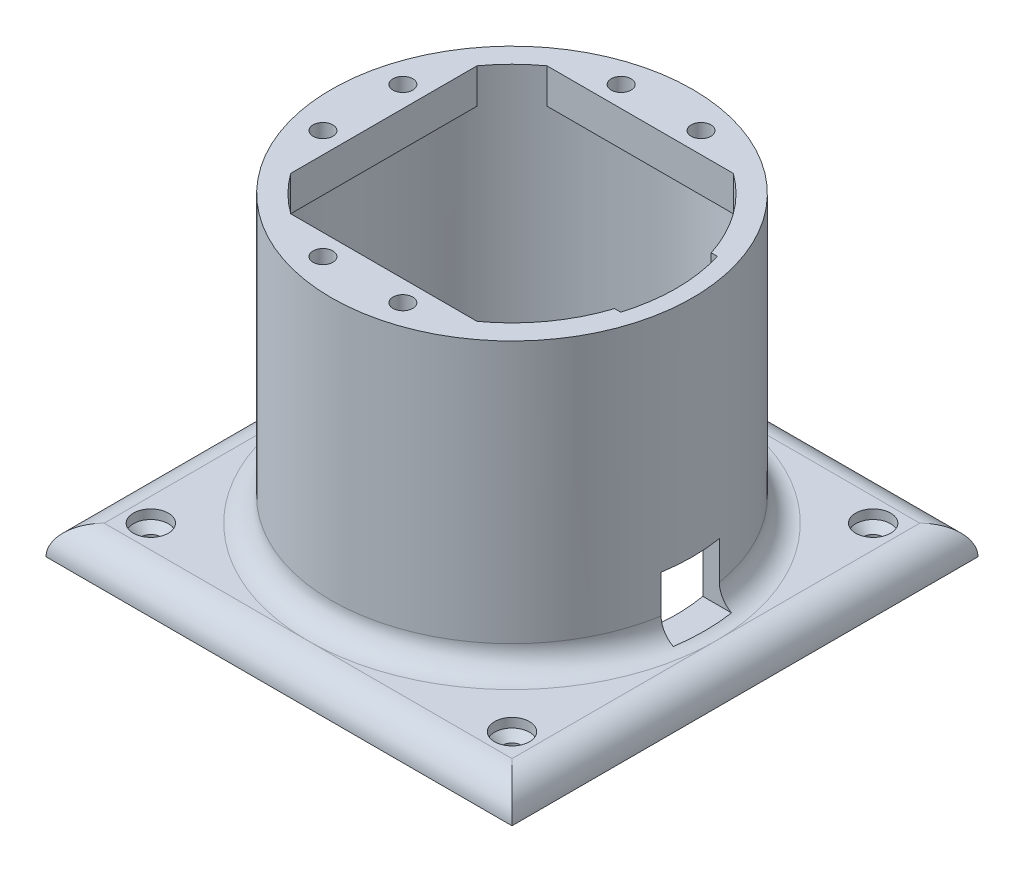
SolidWorks part; units mm, degrees
ref_plane "Front Plane" through (0, 0, 0) normal (0, 0, 1) x (1, 0, 0)
ref_plane "Top Plane" through (0, 0, 0) normal (0, 1, 0) x (1, 0, 0)
ref_plane "Right Plane" through (0, 0, 0) normal (1, 0, 0) x (0, 0, -1)
sketch "Sketch1" plane through (0, 0, 0) normal (0, 1, 0) x (1, 0, 0)
  line L1 (25.9027, 8.3) -> (26.9509, 8.3)
  line L4 (25.9027, -8.3) -> (26.9509, -8.3)
  circle A0 centre (0, 0) radius 31
  arc A1 (25.9027, 8.3) -> (25.9027, -8.3) centre (0, 0) ccw
  arc A3 (26.9509, -8.3) -> (26.9509, 8.3) centre (0, 0) ccw
extrude "Boss-Extrude1" add sketch "Sketch1" against normal blind 54
sketch "Sketch2" plane through (0, 0, 0) normal (0, 1, 0) x (1, 0, 0)
  line L1 (15.995, -22) -> (-15.995, -22)
  line L2 (-15.995, 22) -> (15.995, 22)
  line L3 (-22, -15.995) -> (-22, 15.995)
  line L4 (22, 15.995) -> (22, -15.995) [skipped]
  arc A0 (15.995, 22) -> (-15.995, 22) centre (0, 0) ccw
  arc A2 (-15.995, -22) -> (15.995, -22) centre (0, 0) ccw
  arc A3 (-22, 15.995) -> (-22, -15.995) centre (0, 0) ccw
  arc A4 (22, -15.995) -> (22, 15.995) centre (0, 0) ccw [skipped]
  point P13 (0, 0)
  dimension "D1" = 4
extrude "Boss-Extrude2" add sketch "Sketch2" against normal blind 6
sketch "Sketch3" plane through (0, 0, 0) normal (0, 1, 0) x (1, 0, 0)
  circle A14 centre (-25.597, 6.8587) radius 1.7
  circle A15 centre (-25.597, -6.8587) radius 1.7
  circle A16 centre (-6.8587, 25.597) radius 1.7
  circle A17 centre (6.8587, 25.597) radius 1.7
  circle A18 centre (6.8587, -25.597) radius 1.7
  circle A19 centre (-6.8587, -25.597) radius 1.7
extrude "Cut-Extrude1" cut sketch "Sketch3" against normal blind 4
sketch "Sketch5" plane through (0, -54, 0) normal (0, -1, 0) x (1, 0, 0)
  line L1 (-40, -40) -> (40, -40)
  line L2 (-40, -40) -> (-40, 40)
  line L3 (-40, 40) -> (40, 40)
  line L4 (40, -40) -> (40, 40)
  line L5 (-40, -40) -> (40, 40) construction
  line L6 (-40, 40) -> (40, -40) construction
  circle A0 centre (0, 0) radius 31
  circle A2 centre (-31, 31) radius 3
  circle A3 centre (31, 31) radius 3
  circle A4 centre (31, -31) radius 3
  circle A5 centre (-31, -31) radius 3
  point P0 (0, 0)
  point P20 (0, 0)
  dimension "D1" = 4
extrude "Boss-Extrude3" add sketch "Sketch5" against normal blind 5
fillet "Fillet1" radius 5 4 edges at (40, -49, 0) (0, -49, 40) (0, -49, -40) (-40, -49, 0)
fillet "Fillet2" radius 4 1 edges at (0, -49, 31)
ref_axis "Axis1" through (-31, -49, -31) along (0, -1, 0)
ref_plane "Plane1" through (0, 0, -31) normal (0, 0, 1) x (0, -1, 0)
sketch "Sketch6" plane through (0, 0, -31) normal (0, 0, 1) x (0, -1, 0)
  line L3 (51.885, -29.3) -> (50.585, -28)
  line L4 (50.585, -28) -> (54, -28)
  line L5 (51.885, -29.3) -> (54, -29.3)
  line L10 (54, -28) -> (54, -29.3)
revolve "Revolve1" add sketch "Sketch6" angle 360 about axis through (-31, -49, -31) along (0, -1, 0)
pattern_circular "CirPattern1" count 4 over 360 about axis through (0, -45, 0) along (0, 1, 0) of "Revolve1"
sketch "Sketch7" plane through (0, 0, 0) normal (1, 0, 0) x (0, 0, -1)
  line L0 (0, 0) -> (0, -43.5) construction
  line L1 (31, 0) -> (-31, 0) construction
  line L3 (-5, -48.5) -> (5, -48.5)
  line L4 (-5, -48.5) -> (-5, -38.5)
  line L5 (-5, -38.5) -> (5, -38.5)
  line L6 (5, -48.5) -> (5, -38.5)
  line L7 (-5, -48.5) -> (5, -38.5) construction
  line L8 (-5, -38.5) -> (5, -48.5) construction
extrude "Cut-Extrude2" cut sketch "Sketch7" along normal blind 35
